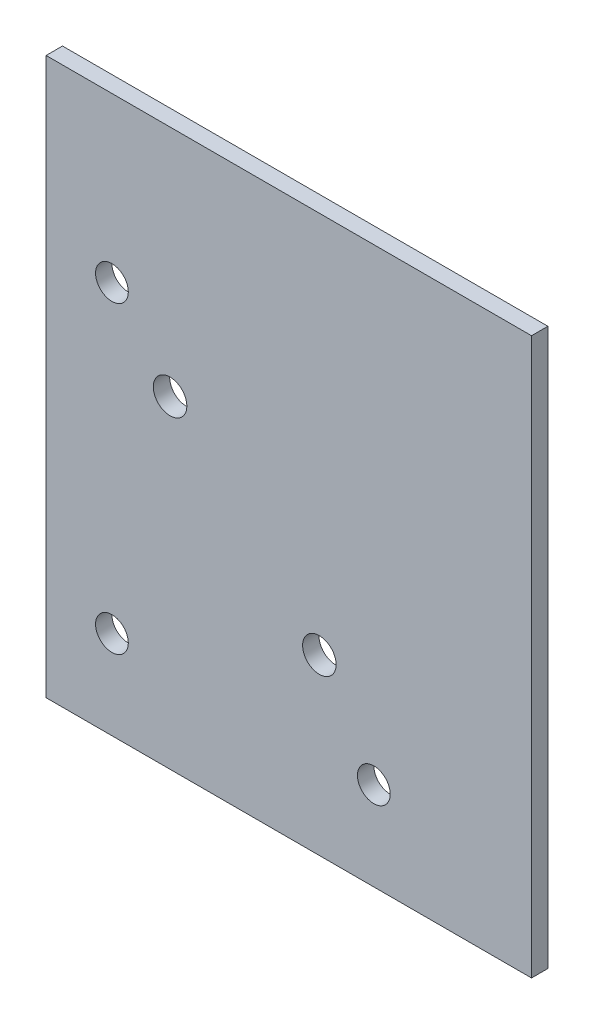
SolidWorks part; units mm, degrees
ref_plane "Front Plane" through (0, 0, 0) normal (0, 0, 1) x (1, 0, 0)
ref_plane "Top Plane" through (0, 0, 0) normal (0, 1, 0) x (1, 0, 0)
ref_plane "Right Plane" through (0, 0, 0) normal (1, 0, 0) x (0, 0, -1)
sketch "Sketch1" plane through (0, 0, 0) normal (0, 0, 1) x (1, 0, 0)
  line L1 (5.1833, 100.7604) -> (-88.9667, 100.7604)
  line L2 (5.1833, 100.7604) -> (5.1833, 208.6503)
  line L3 (5.1833, 208.6503) -> (-88.9667, 208.6503)
  line L4 (-88.9667, 100.7604) -> (-88.9667, 208.6503)
  line L5 (2.1325, 150.6967) -> (-48.6675, 150.6967) construction
  line L6 (-48.6675, 201.4967) -> (-48.6675, 150.6967) construction
  circle A3 centre (-76.2, 117.9286) radius 3.175
  circle A4 centre (-25.4, 117.9286) radius 3.175
  circle A5 centre (-76.2, 176.8929) radius 3.175
  circle A6 centre (-64.9235, 163.3967) radius 3.2512
  circle A7 centre (-35.9675, 134.4407) radius 3.2512
  dimension "D1" = 6.5024
  dimension "D2" = 16.256
  dimension "D3" = 12.7
  dimension "D4" = 16.256
  dimension "D5" = 12.7
extrude "Boss-Extrude1" add sketch "Sketch1" along normal blind 3.175
equation "\"80/20 to Center Hole\"= .64in"
equation "\"80/20 from Edge\"= 0.5in"
equation "\"D2@Sketch1\"=\"80/20 to Center Hole\""
equation "\"D3@Sketch1\"=\"80/20 from Edge\""
equation "\"D4@Sketch1\"=\"80/20 to Center Hole\""
equation "\"D5@Sketch1\"=\"80/20 from Edge\""
